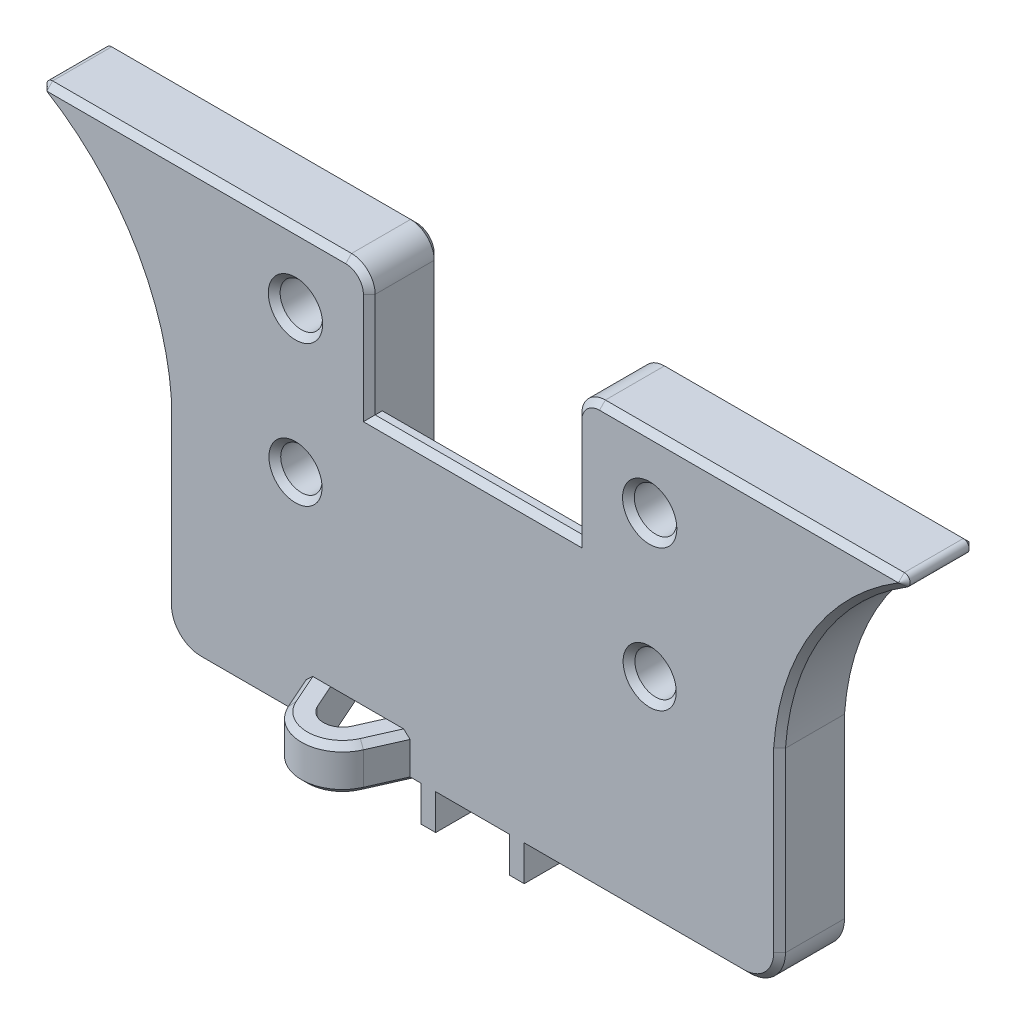
SolidWorks part; units mm, degrees
ref_plane "Front Plane" through (0, 0, 0) normal (0, 0, 1) x (1, 0, 0)
ref_plane "Top Plane" through (0, 0, 0) normal (0, 1, 0) x (1, 0, 0)
ref_plane "Right Plane" through (0, 0, 0) normal (1, 0, 0) x (0, 0, -1)
sketch "Sketch2" plane through (0, 0, 0) normal (0, 0, 1) x (1, 0, 0)
  line L0 (0, -33.2846) -> (0, 67.9981) construction
  line L12 (45.8007, 37.8996) -> (-45.8007, 37.8996)
  line L13 (-33.02, 15.1445) -> (-33.02, -3.9055)
  line L14 (-29.21, -7.7155) -> (29.21, -7.7155)
  line L15 (33.02, 15.1445) -> (33.02, -3.9055)
  circle A4 centre (-19.05, 15.1445) radius 2.2225
  circle A12 centre (19.05, 15.1445) radius 2.2225
  arc A13 (-33.02, 15.1445) -> (-46.1321, 36.723) centre (-60.5269, 13.203) ccw
  arc A14 (33.02, 15.1445) -> (46.1321, 36.723) centre (60.5269, 13.203) cw
  arc A15 (33.02, -3.9055) -> (29.21, -7.7155) centre (29.21, -3.9055) cw
  arc A16 (-33.02, -3.9055) -> (-29.21, -7.7155) centre (-29.21, -3.9055) ccw
  arc A17 (46.1321, 36.723) -> (45.8007, 37.8996) centre (45.8007, 37.2646) ccw
  arc A18 (-45.8007, 37.8996) -> (-46.1321, 36.723) centre (-45.8007, 37.2646) ccw
  point P4 (0, 57.6776)
  point P9 (0, 19.5776)
  point P12 (0, 37.8996)
  point P16 (0, -7.7155)
  point P18 (33.02, -7.7155)
  point P20 (0, -3.9055)
  point P22 (-33.02, -7.7155)
  point P27 (48.26, 37.8996)
  point P30 (-48.26, 37.8996)
  dimension "D2" = 48.26
  dimension "D3" = 22.86
  dimension "D6" = 0.635
  dimension "D4" = 33.02
  dimension "D5" = 3.81
  dimension "D7" = 27.5753
  dimension "D8" = 19.05
  dimension "D9" = 45.8007
  dimension "D10" = 19.05
  dimension "D11" = 19.5776
  dimension "D12" = 57.6776
  dimension "D1" = 4.445
extrude "Boss-Extrude1" add sketch "Sketch2" along normal blind 7.62
sketch "Sketch11" plane through (0, 0, 7.62) normal (0, 0, 1) x (1, 0, 0)
  line L0 (0, 41.9648) -> (0, -47.1588) construction
  line L1 (-19.05, 15.1445) -> (-19.05, 30.3845) construction
  circle A0 centre (-19.05, 30.3845) radius 2.286
  circle A1 centre (19.05, 30.3845) radius 2.286
  dimension "D2" = 4.572
  dimension "D1" = 15.24
extrude "Cut-Extrude9" cut sketch "Sketch11" against normal through all
sketch "Sketch12" plane through (0, 0, 0) normal (0, 0, 1) x (1, 0, 0)
  line L0 (0, 39.594) -> (0, -43.4023) construction
  line L1 (-4.7625, 33.4498) -> (4.7625, 33.4498)
  line L3 (4.7625, 10.9708) -> (-4.7625, 10.9708)
  line L4 (-11.1125, 17.3208) -> (-11.1125, 27.0998)
  line L5 (11.1125, 17.3208) -> (11.1125, 27.0998)
  arc A0 (11.1125, 27.0998) -> (4.7625, 33.4498) centre (4.7625, 27.0998) ccw
  arc A1 (11.1125, 17.3208) -> (4.7625, 10.9708) centre (4.7625, 17.3208) cw
  arc A2 (-4.7625, 10.9708) -> (-11.1125, 17.3208) centre (-4.7625, 17.3208) cw
  arc A3 (-4.7625, 33.4498) -> (-11.1125, 27.0998) centre (-4.7625, 27.0998) ccw
  point P10 (0, 10.9708)
  point P11 (0, 33.4498)
  point P13 (11.1125, 33.4498)
  point P16 (11.1125, 10.9708)
  point P19 (-11.1125, 10.9708)
  point P22 (-11.1125, 33.4498)
  dimension "D4" = 6.35
  dimension "D1" = 11.1125
  dimension "D2" = 10.9708
  dimension "D3" = 22.479
extrude "Cut-Extrude11" cut sketch "Sketch12" along normal blind 6.223
sketch "Sketch13" plane through (0, 0, 0) normal (0, 0, -1) x (-1, 0, 0)
  line L2 (-11.1125, 40.3062) -> (-11.1125, 24.1288)
  line L3 (-11.1125, 24.1288) -> (11.1125, 24.1288)
  line L7 (-11.1125, 40.3062) -> (11.1125, 40.3062)
  line L8 (11.1125, 40.3062) -> (11.1125, 24.1288)
  dimension "D1" = 11.1125
  dimension "D2" = 11.1125
  dimension "D3" = 24.1288
  dimension "D4" = 40.3062
extrude "Cut-Extrude12" cut sketch "Sketch13" against normal through all
sketch "Sketch15" plane through (0, -7.7155, 0) normal (0, -1, 0) x (1, 0, 0)
  line L0 (0, -11.1019) -> (0, 17.7532) construction
  line L1 (-29.21, 3.81) -> (29.21, 3.81) construction
  line L4 (-29.21, 7.62) -> (-29.21, 0) construction
  line L5 (29.21, 7.62) -> (29.21, 0) construction
  circle A0 centre (0, 3.81) radius 2.032
  dimension "D1" = 4.064
extrude "Cut-Extrude14" cut sketch "Sketch15" against normal blind 17.78
sketch "Sketch16" plane through (0, 0, 0) normal (0, 0, -1) x (-1, 0, 0)
  line L0 (29.21, -7.7155) -> (-29.21, -7.7155) construction
  line L1 (-3.9687, -7.7155) -> (-5.5563, -7.7155)
  line L2 (-3.9687, -7.7155) -> (-3.9688, -10.8905)
  line L3 (-3.9688, -10.8905) -> (-5.5563, -10.8905)
  line L4 (-5.5563, -7.7155) -> (-5.5563, -10.8905)
  line L5 (0, -11.3212) -> (0, 10.1435) construction
  line L6 (5.5562, -7.7155) -> (3.9688, -7.7155)
  line L7 (5.5562, -7.7155) -> (5.5562, -10.8905)
  line L8 (5.5562, -10.8905) -> (3.9688, -10.8905)
  line L9 (3.9688, -7.7155) -> (3.9688, -10.8905)
  dimension "D1" = 1.5875
  dimension "D2" = 3.175
  dimension "D3" = 7.9375
  dimension "D4" = 3.9688
extrude "Boss-Extrude2" add sketch "Sketch16" against normal up to surface (7.62 mm away) up to face at (-16.764, 30.3845, 7.62)
fillet "Fillet1" radius 2.54 2 edges at (11.1125, 37.8996, 3.81) (-11.1125, 37.8996, 3.81)
sketch "Sketch17" plane through (0, -7.7155, 0) normal (0, -1, 0) x (1, 0, 0)
  line L0 (0, 3.81) -> (-12.3, 9.3126) construction
  line L1 (0, 3.81) -> (12.3, 9.3126) construction
  line L2 (-14.1577, 10.136) -> (-18.6499, 0)
  line L3 (-29.21, 0) -> (-5.5562, 0) construction
  line L4 (-10.4422, 10.136) -> (-5.9499, 0)
  line L5 (-18.6499, 0) -> (-5.9499, 0)
  line L6 (-14.1577, 10.136) -> (-10.4422, 10.136)
  line L7 (0, 3.81) -> (0, 0) construction
  line L8 (5.95, 0) -> (10.4422, 10.136) construction
  line L9 (5.5563, 0) -> (29.21, 0) construction
  line L10 (14.1577, 10.136) -> (18.65, 0) construction
  line L11 (18.65, 0) -> (5.95, 0) construction
  line L12 (10.4422, 10.136) -> (14.1577, 10.136) construction
  circle A0 centre (-12.3, 9.3126) radius 2.032 construction
  circle A1 centre (12.3, 9.3126) radius 2.032 construction
  dimension "D3" = 4.064
  dimension "D1" = 13.4747
  dimension "D2" = 24.5999
  dimension "D4" = 12.7
  dimension "D5" = 12.7
extrude "Cut-Extrude15" cut sketch "Sketch17" against normal blind 4.7625
sketch "Sketch18" plane through (0, -7.7155, 0) normal (0, -1, 0) x (1, 0, 0)
  line L0 (-15.2727, 7.62) -> (-14.1577, 10.136)
  line L1 (-5.9499, 0) -> (-9.3272, 7.62) construction
  line L2 (-9.3272, 7.62) -> (-10.4422, 10.136)
  line L4 (-17.8774, 7.62) -> (-16.3347, 11.1008)
  line L5 (-29.21, 7.62) -> (-15.2727, 7.62) construction
  line L6 (-8.2652, 11.1008) -> (-6.7225, 7.62)
  line L7 (-9.3272, 7.62) -> (-5.5562, 7.62) construction
  line L8 (-17.8774, 7.62) -> (-15.2727, 7.62)
  line L9 (-9.3272, 7.62) -> (-6.7225, 7.62)
  line L10 (-14.1577, 10.136) -> (-16.3347, 11.1008) construction
  arc A0 (-10.4422, 10.136) -> (-14.1577, 10.136) centre (-12.3, 9.3126) ccw
  arc A1 (-16.3347, 11.1008) -> (-8.2652, 11.1008) centre (-12.3, 9.3126) cw
  point P2 (-15.3768, 7.62)
  point P3 (-9.2231, 7.62)
  dimension "D1" = 4.064
  dimension "D2" = 2.3813
  dimension "D3" = 2.3813
extrude "Boss-Extrude3" add sketch "Sketch18" against normal up to surface (4.7625 mm away) up to face at (-12.3, -2.953, 3.81)
chamfer "Chamfer1" distance 0.635 angle 45 54 edges at (-16.8275, 15.1445, 7.62) (-16.8275, 15.1445, 0) (-16.764, 30.3845, 7.62) (-16.764, 30.3845, 0) (16.764, 30.3845, 7.62) (16.764, 30.3845, 0) (16.8275, 15.1445, 7.62) (16.8275, 15.1445, 0) (0, -7.7155, 7.62) (0, -7.7155, 0) (11.1125, 26.3402, 0) (9.2526, 12.8307, 0) (0, 10.9708, 0) (-9.2526, 12.8307, 0) (-11.1125, 26.3402, 0) (33.02, 5.6195, 0) (33.02, 5.6195, 7.62) (31.9041, -6.5996, 0) (31.9041, -6.5996, 7.62) (29.7266, 37.8996, 0) (29.7266, 37.8996, 7.62) (46.4119, 37.4368, 0) (46.4119, 37.4368, 7.62) (36.9611, 27.5227, 0) (36.9611, 27.5227, 7.62) (-5.7531, -7.7155, 0) (-6.1394, -7.7155, 7.62) (-23.5437, -7.7155, 7.62) (-23.93, -7.7155, 0) (-29.7266, 37.8996, 7.62) (-29.7266, 37.8996, 0) (-31.9041, -6.5996, 0) (-31.9041, -6.5996, 7.62) (-46.4119, 37.4368, 0) (-46.4119, 37.4368, 7.62) (-33.02, 5.6195, 0) (-33.02, 5.6195, 7.62) (-36.9611, 27.5227, 0) (-36.9611, 27.5227, 7.62) (17.3831, -7.7155, 7.62) (11.1125, 29.7442, 7.62) (0, 24.1288, 7.62) (-11.1125, 29.7442, 7.62) (11.8564, 37.1556, 0) (11.8564, 37.1556, 7.62) (-11.8564, 37.1556, 7.62) (-11.8564, 37.1556, 0) (-7.4939, -2.953, 9.3604) (-7.4939, -7.7155, 9.3604) (-17.106, -2.953, 9.3604) (-17.106, -7.7155, 9.3604) (-12.3, -2.953, 13.7259) (-12.3, -7.7155, 13.7259) (17.3831, -7.7155, 0)
equation "\"D4@Sketch16\"=\"D3@Sketch16\"/2"
